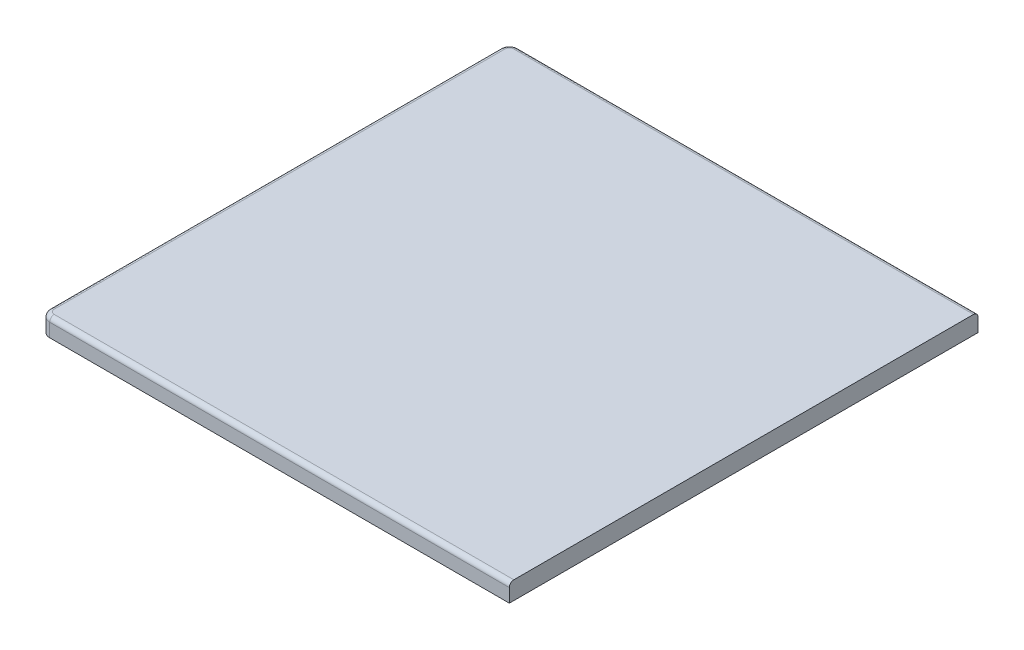
SolidWorks part; units mm, degrees
ref_plane "Piano frontale" through (0, 0, 0) normal (0, 0, 1) x (1, 0, 0)
ref_plane "Piano superiore" through (0, 0, 0) normal (0, 1, 0) x (1, 0, 0)
ref_plane "Piano destro" through (0, 0, 0) normal (1, 0, 0) x (0, 0, -1)
sketch "Schizzo1" plane through (0, 0, 0) normal (0, 1, 0) x (1, 0, 0)
  line L1 (52, -52) -> (-52, -52)
  line L2 (52, -52) -> (52, 52)
  line L3 (52, 52) -> (-52, 52)
  line L4 (-52, -52) -> (-52, 52)
  line L5 (52, -52) -> (-52, 52) construction
  line L6 (52, 52) -> (-52, -52) construction
  point P0 (0, 0)
  dimension "D1" = 104
  dimension "D2" = 104
extrude "Estrusione-Estrusione1" add sketch "Schizzo1" along normal blind 4
sketch "Schizzo2" plane through (0, 0, 0) normal (0, 1, 0) x (1, 0, 0)
  line L0 (-52, -52) -> (52, -52) construction
  line L1 (-52, 52) -> (-52, -52) construction
  line L2 (-50, -50) -> (50, -50)
  line L3 (50, -50) -> (50, 50)
  line L4 (50, 50) -> (-50, 50)
  line L5 (-50, 50) -> (-50, -50)
  line L6 (-52, -52) -> (52, -52)
  line L7 (52, -52) -> (52, 52)
  line L8 (52, 52) -> (-52, 52)
  line L9 (-52, 52) -> (-52, -52)
  point P0 (-50, -52)
  point P1 (-52, -50)
  dimension "D1" = 2
  dimension "D2" = 2
  dimension "D3" = 100
  dimension "D4" = 100
extrude "Taglio-Estrusione2" cut sketch "Schizzo2" along normal blind 3 contours L5 L2 L3 L4
fillet "Raccordo1" radius 1 3 edges at (0, 4, 52) (-52, 4, 0) (0, 4, -52)
fillet "Raccordo2" radius 2 4 edges at (-51.7071, 3.7071, -51.7071) (-51.7071, 3.7071, 51.7071) (-52, 1.5, 52) (-52, 1.5, -52)
